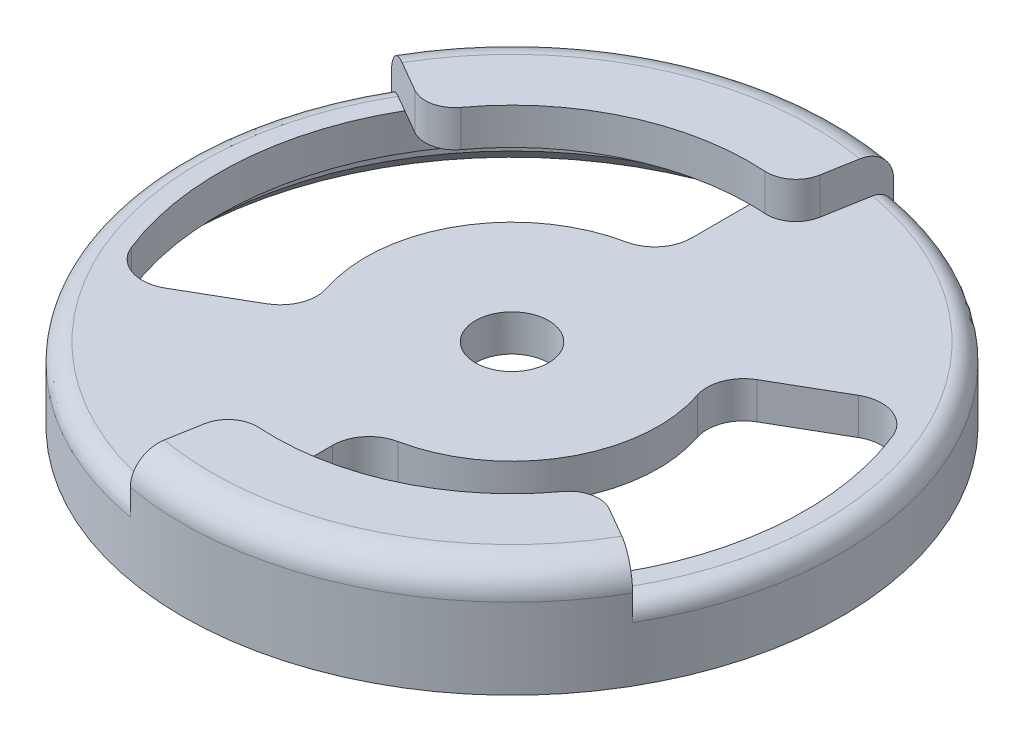
SolidWorks part; units mm, degrees
material "ABS PC"
ref_plane "前视基准面" through (0, 0, 0) normal (0, 0, 1) x (1, 0, 0)
ref_plane "上视基准面" through (0, 0, 0) normal (0, 1, 0) x (1, 0, 0)
ref_plane "右视基准面" through (0, 0, 0) normal (1, 0, 0) x (0, 0, -1)
sketch "草图1" plane through (0, 0, 0) normal (0, 1, 0) x (1, 0, 0)
  circle A0 centre (0, 0) radius 9
  dimension "D1" = 18
extrude "凸台-拉伸1" add sketch "草图1" along normal blind 2
sketch "草图2" plane through (0, 0, 0) normal (0, -1, 0) x (1, 0, 0)
  circle A0 centre (0, 0) radius 8.5
  dimension "D1" = 17
extrude "切除-拉伸1" cut sketch "草图2" against normal blind 1
chamfer "倒角1" distance 0.5 angle 45 1 edges at (0, 0, -8.5)
sketch "草图3" plane through (0, 2, 0) normal (0, 1, 0) x (1, 0, 0)
  line L0 (0, 8) -> (0, -8)
  line L1 (6.9282, 4) -> (-6.9282, -4)
  circle A0 centre (0, 0) radius 4
  circle A1 centre (0, 0) radius 8
  dimension "D1" = 8
  dimension "D2" = 16
  dimension "D3" = 60
extrude "切除-拉伸2" cut sketch "草图3" against normal blind 1 contours L0 A1 L1 A0 | L0 A1 L1 A0 region at (-4.4563, 2, -2.5729) region at (4.4563, 2, 2.5729)
fillet "圆角1" radius 1 8 edges at (-6.9282, 1.5, 4) (6.9282, 1.5, -4) (0, 1.5, -8) (0, 1.5, 8) (-3.4641, 1.5, 2) (3.4641, 1.5, -2) (0, 1.5, -4) (0, 1.5, 4)
sketch "草图4" plane through (0, 2, 0) normal (0, 1, 0) x (1, 0, 0)
  circle A0 centre (0, 0) radius 1
  dimension "D1" = 2
extrude "切除-拉伸3" cut sketch "草图4" against normal through all
sketch "草图5" plane through (0, 2, 0) normal (0, 1, 0) x (1, 0, 0)
  line L0 (-7.7942, 4.5) -> (7.7942, -4.5)
  line L1 (1.5628, 8.8633) -> (-1.5628, -8.8633)
  line L2 (-4.2426, -2.4495) -> (-6, -3.4641) construction
  circle A0 centre (0, 0) radius 9
  circle A1 centre (0, 0) radius 6.5
  line M4 (0, -6.9282) -> (0, -4.899)
  arc M10 (7.4286, 2.9692) -> (1.1429, -7.9179) centre (0, 0) cw
  arc M11 (1.1429, -7.9179) -> (0, -6.9282) centre (1, -6.9282) cw
  circle M12 centre (0, 0) radius 9
  arc M13 (-7.4286, -2.9692) -> (-1.1429, 7.9179) centre (0, 0) cw
  arc M14 (-1.1429, 7.9179) -> (0, 6.9282) centre (-1, 6.9282) cw
  line M15 (0, 6.9282) -> (0, 4.899)
  dimension "D1" = 13
  dimension "D2" = 60
  dimension "D3" = 70
extrude "凸台-拉伸2" add sketch "草图5" along normal blind 1 contours A1 L1 L0 M12 M13 M14 M15 | A1 L0 M15 M14 M13 | A1 L0 M4 M11 M10 | A1 L1 L0 M12 M10 M11 M4 region at (-3.7587, 2, -8.0606) region at (-3.5509, 2, -5.9756) region at (-1.2413, 2, 7.6507) region at (3.5509, 2, 5.9756)
fillet "圆角3" radius 0.8 2 edges at (3.8036, 3, 8.1568) (-3.8036, 3, -8.1568)
fillet "圆角4" radius 0.8 4 edges at (5.6292, 2.5, 3.25) (-1.1287, 2.5, 6.4013) (1.1287, 2.5, -6.4013) (-5.6292, 2.5, -3.25)
fillet "圆角5" radius 0.5 2 edges at (8.1568, 2, -3.8036) (-8.1568, 2, 3.8036)
